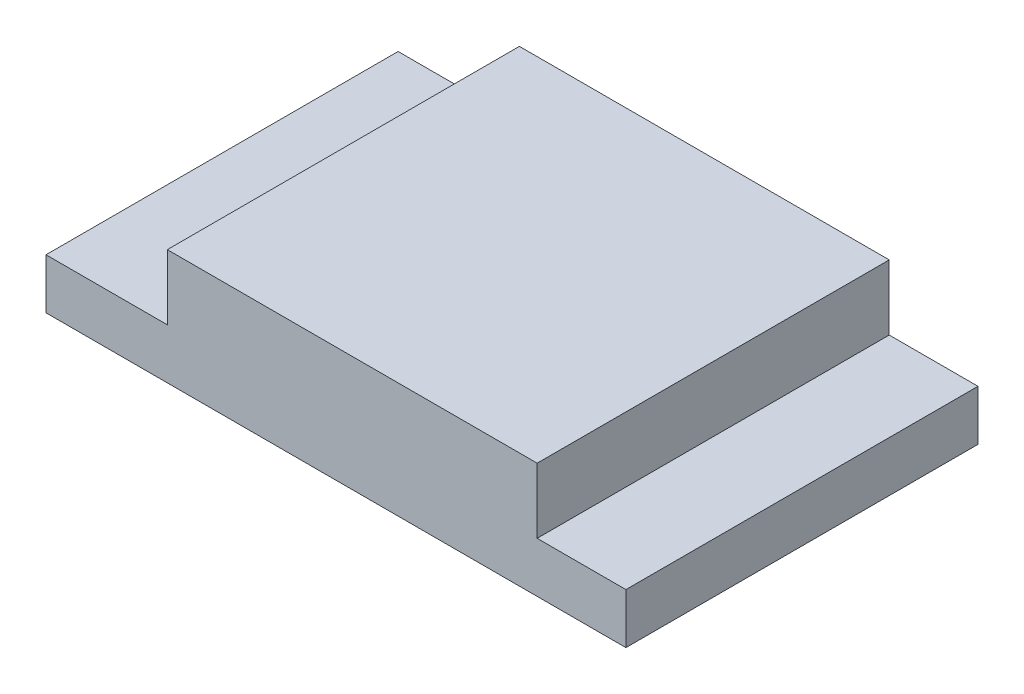
SolidWorks part; units mm, degrees
ref_plane "Front Plane" through (0, 0, 0) normal (0, 0, 1) x (1, 0, 0)
ref_plane "Top Plane" through (0, 0, 0) normal (0, 1, 0) x (1, 0, 0)
ref_plane "Right Plane" through (0, 0, 0) normal (1, 0, 0) x (0, 0, -1)
sketch "Sketch1" plane through (0, 0, 0) normal (0, 1, 0) x (1, 0, 0)
  line L1 (0, 0) -> (19.6, 0)
  line L2 (0, 0) -> (0, 11.9)
  line L3 (0, 11.9) -> (19.6, 11.9)
  line L4 (19.6, 0) -> (19.6, 11.9)
  dimension "D1" = 11.9
  dimension "D2" = 19.6
extrude "Boss-Extrude1" add sketch "Sketch1" along normal blind 1.7
sketch "Sketch2" plane through (0, 1.7, 0) normal (0, 1, 0) x (1, 0, 0)
  line L0 (19.6, 11.9) -> (0, 11.9) construction
  line L1 (4.1, 11.9) -> (16.6, 11.9)
  line L2 (4.1, 11.9) -> (4.1, 0)
  line L3 (4.1, 0) -> (16.6, 0)
  line L4 (16.6, 11.9) -> (16.6, 0)
  line L5 (0, 0) -> (19.6, 0) construction
  line L6 (19.6, 0) -> (19.6, 11.9) construction
  dimension "D1" = 12.5
  dimension "D2" = 3
extrude "Boss-Extrude2" add sketch "Sketch2" along normal blind 2.2
ref_plane "Plane1" through (0, 0, -5.95) normal (0, 0, -1) x (-1, 0, 0)
ref_plane "Plane2" through (9.8, 0, 0) normal (1, 0, 0) x (0, 0, -1)
